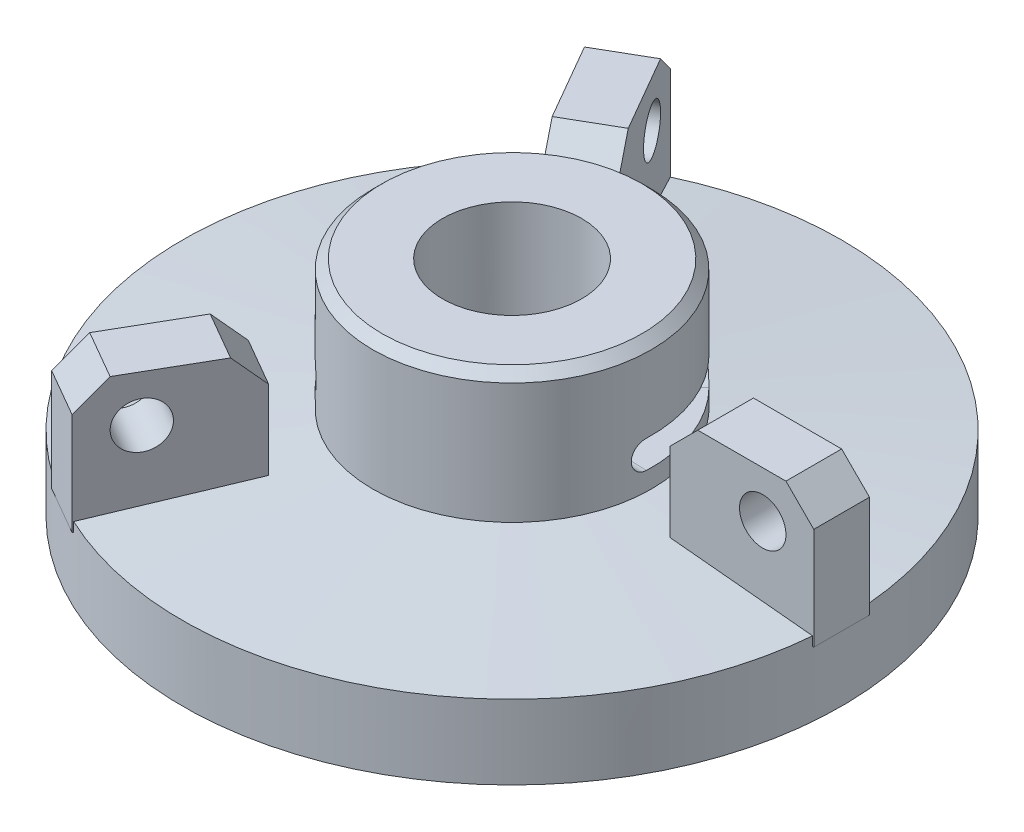
SolidWorks part; units mm, degrees
material "SUS304"
ref_plane "Front" through (0, 0, 0) normal (0, 0, 1) x (1, 0, 0)
ref_plane "Top" through (0, 0, 0) normal (0, 1, 0) x (1, 0, 0)
ref_plane "Right" through (0, 0, 0) normal (1, 0, 0) x (0, 0, -1)
sketch "Sketch1" plane through (0, 0, 0) normal (0, 0, 1) x (1, 0, 0)
  line L0 (0, -5.1764) -> (0, 52.1426) construction
  line L1 (0, 0) -> (35.5, 0)
  line L2 (35.5, 0) -> (35.5, 8)
  line L3 (35.5, 8) -> (15, 9.9992)
  line L4 (15, 9.9992) -> (15, 24)
  line L5 (15, 24) -> (0, 24)
  line L6 (0, 24) -> (0, 0)
  dimension "D1" = 30
  dimension "D2" = 71
  dimension "D3" = 24
  dimension "D4" = 8
  dimension "D5" = 95.57
revolve "Revolve1" add sketch "Sketch1" angle 360 about L0
sketch "Sketch2" plane through (0, 0, 0) normal (0, 0, 1) x (1, 0, 0)
  line L0 (35.5, 0) -> (35.5, 8) construction
  line L1 (35.5, 7) -> (20, 7)
  line L2 (35.5, 7) -> (35.5, 21)
  line L3 (35.5, 21) -> (20, 21)
  line L4 (20, 7) -> (20, 21)
  line L5 (-35.5, 0) -> (35.5, 0) construction
  dimension "D1" = 20
  dimension "D2" = 7
  dimension "D3" = 14
extrude "Boss-Extrude1" add sketch "Sketch2" along normal mid plane 6
pattern_circular "CirPattern1" count 3 over 360 about axis through (0, -5.1764, 0) along (0, -1, 0) of "Boss-Extrude1"
sketch "Sketch3" plane through (0, 0, 0) normal (0, 0, 1) x (1, 0, 0)
  line L0 (0, -2.419) -> (0, 27.0791) construction
  line L1 (0, 0) -> (22.5, 0)
  line L2 (-35.5, 0) -> (35.5, 0) construction
  line L3 (22.5, 0) -> (22.5, 3)
  line L4 (22.5, 3) -> (7.5, 3)
  line L5 (7.5, 3) -> (7.5, 24)
  line L6 (15, 24) -> (-15, 24) construction
  line L7 (7.5, 24) -> (0, 24)
  line L8 (0, 24) -> (0, 0)
  dimension "D1" = 15
  dimension "D2" = 45
  dimension "D3" = 3
revolve "Cut-Revolve1" cut sketch "Sketch3" angle 360 about L0
sketch "Sketch4" plane through (0, 3, 0) normal (0, -1, 0) x (1, 0, 0)
  line L0 (-7.4246, 7.4246) -> (7.4246, -7.4246) construction
  line L1 (-6.364, 8.4853) -> (8.4853, -6.364)
  line L2 (-8.4853, 6.364) -> (6.364, -8.4853)
  line L6 (-22.5, 0) -> (22.5, 0) construction
  arc A0 (-6.364, 8.4853) -> (-8.4853, 6.364) centre (-7.4246, 7.4246) ccw
  arc A1 (6.364, -8.4853) -> (8.4853, -6.364) centre (7.4246, -7.4246) ccw
  circle A2 centre (0, 0) radius 22.5 construction
  circle A3 centre (0, 0) radius 22.5 construction
  point P2 (0, 0)
  dimension "D2" = 21
  dimension "D1" = 3
  dimension "D3" = 45
extrude "Cut-Extrude1" cut sketch "Sketch4" against normal blind 12
sketch "Sketch5" plane through (0, 24, 0) normal (0, 1, 0) x (1, 0, 0)
  line L0 (9.4928, 11.6141) -> (4.1355, 6.2568)
  line L1 (-8.4853, -6.364) -> (6.364, 8.4853) construction
  line L2 (14.8634, -2.02) -> (7.2916, -1.7555)
  line L3 (-4.1355, -6.2568) -> (-9.4928, -11.6141)
  line L4 (-23.9092, 0) -> (23.6765, 0) construction
  line L5 (-6.364, -8.4853) -> (8.4853, 6.364) construction
  line L6 (-14.8634, 2.02) -> (-7.2916, 1.7555)
  arc A0 (-14.8634, 2.02) -> (-9.4928, -11.6141) centre (0, 0) ccw
  circle A1 centre (0, 0) radius 15 construction
  circle A2 centre (0, 0) radius 15 construction
  circle A3 centre (0, 0) radius 7.5 construction
  arc A4 (14.8634, -2.02) -> (9.4928, 11.6141) centre (0, 0) ccw
  arc A5 (7.2916, -1.7555) -> (4.1355, 6.2568) centre (0, 0) ccw
  arc A6 (-7.2916, 1.7555) -> (-4.1355, -6.2568) centre (0, 0) ccw
  dimension "D1" = 47
  dimension "D2" = 3
extrude "Cut-Extrude2" cut sketch "Sketch5" against normal blind 3 from offset 9 offset against normal yes
sketch "Sketch6" plane through (-2.5981, 0, -1.5) normal (0.866, 0, 0.5) x (0.5, 0, -0.866)
  line L0 (-35.5, 0) -> (35.5, 0) construction
  circle A0 centre (-30, 16) radius 2.5
  dimension "D3" = 5
  dimension "D1" = 30
  dimension "D2" = 16
extrude "Cut-Extrude3" cut sketch "Sketch6" along normal up to next
pattern_circular "CirPattern2" count 3 over 360 about axis through (0, -5.1764, 0) along (0, -1, 0) of "Cut-Extrude3"
fillet "Fillet1" radius 1.5 8 edges at (11.0775, 15, 1.8877) (11.0775, 12, 1.8877) (6.8141, 15, -8.9355) (7.9284, 12, -10.0497) (-6.8141, 15, 8.9355) (-7.9284, 12, 10.0497) (-11.0775, 15, -1.8877) (-11.0775, 12, -1.8877)
chamfer "Chamfer1" distance 3 angle 45 6 edges at (35.5, 21, 0) (20, 21, 0) (-10, 21, 17.3205) (-17.75, 21, 30.7439) (-10, 21, -17.3205) (-17.75, 21, -30.7439)
chamfer "Chamfer2" distance 1 angle 45 1 edges at (0, 24, -15)
